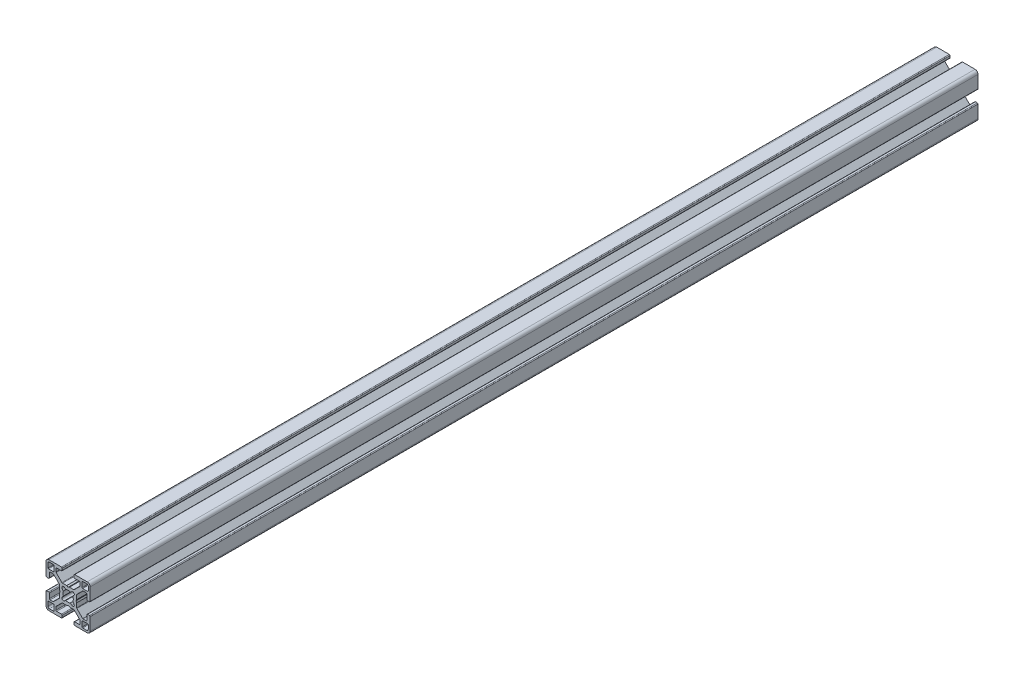
SolidWorks part; units mm, degrees
ref_plane "Plano frontal" through (0, 0, 0) normal (0, 0, 1) x (1, 0, 0)
ref_plane "Plano superior" through (0, 0, 0) normal (0, 1, 0) x (1, 0, 0)
ref_plane "Plano direito" through (0, 0, 0) normal (1, 0, 0) x (0, 0, -1)
ref_plane "Plano1"
sketch "Esboço1" plane through (0, 0, 0) normal (0, 0, 1) x (1, 0, 0)
  line L0 (-13, -15) -> (-4.508, -15)
  line L1 (-4, -14.492) -> (-4, -13.251)
  line L2 (-4.508, -12.743) -> (-7.742, -12.743)
  line L3 (-8.25, -12.235) -> (-8.25, -10.2642)
  line L4 (-8.1012, -9.905) -> (-4.1795, -5.9833)
  line L5 (-3.8203, -5.8345) -> (-0.949, -5.8345)
  line L6 (-0.949, -5.8345) -> (0, -5.325)
  line L7 (0, -5.325) -> (0.949, -5.8345)
  line L8 (0.949, -5.8345) -> (3.8216, -5.8345)
  line L9 (4.1808, -5.9833) -> (8.1012, -9.9037)
  line L10 (8.25, -10.2629) -> (8.25, -12.235)
  line L11 (7.742, -12.743) -> (4.508, -12.743)
  line L12 (4, -13.251) -> (4, -14.492)
  line L13 (4.508, -15) -> (13, -15)
  line L14 (15, -13) -> (15, -4.508)
  line L15 (14.492, -4) -> (13.251, -4)
  line L16 (12.743, -4.508) -> (12.743, -7.742)
  line L17 (12.235, -8.25) -> (10.2642, -8.25)
  line L18 (9.905, -8.1012) -> (5.9833, -4.1795)
  line L19 (5.8345, -3.8203) -> (5.8345, -0.949)
  line L20 (5.8345, -0.949) -> (5.325, 0)
  line L21 (5.325, 0) -> (5.8345, 0.949)
  line L22 (5.8345, 0.949) -> (5.8345, 3.8216)
  line L23 (5.9833, 4.1808) -> (9.9037, 8.1012)
  line L24 (10.2629, 8.25) -> (12.235, 8.25)
  line L25 (12.743, 7.742) -> (12.743, 4.508)
  line L26 (13.251, 4) -> (14.492, 4)
  line L27 (15, 4.508) -> (15, 13)
  line L28 (13, 15) -> (4.508, 15)
  line L29 (4, 14.492) -> (4, 13.251)
  line L30 (4.508, 12.743) -> (7.742, 12.743)
  line L31 (8.25, 12.235) -> (8.25, 10.2642)
  line L32 (8.1012, 9.905) -> (4.1795, 5.9833)
  line L33 (3.8203, 5.8345) -> (0.949, 5.8345)
  line L34 (0.949, 5.8345) -> (0, 5.325)
  line L35 (0, 5.325) -> (-0.949, 5.8345)
  line L36 (-0.949, 5.8345) -> (-3.8216, 5.8345)
  line L37 (-4.1808, 5.9833) -> (-8.1012, 9.9037)
  line L38 (-8.25, 10.2629) -> (-8.25, 12.235)
  line L39 (-7.742, 12.743) -> (-4.508, 12.743)
  line L40 (-4, 13.251) -> (-4, 14.492)
  line L41 (-4.508, 15) -> (-13, 15)
  line L42 (-15, 13) -> (-15, 4.508)
  line L43 (-14.492, 4) -> (-13.251, 4)
  line L44 (-12.743, 4.508) -> (-12.743, 7.742)
  line L45 (-12.235, 8.25) -> (-10.2642, 8.25)
  line L46 (-9.905, 8.1012) -> (-5.9833, 4.1795)
  line L47 (-5.8345, 3.8203) -> (-5.8345, 0.949)
  line L48 (-5.8345, 0.949) -> (-5.325, 0)
  line L49 (-5.325, 0) -> (-5.8345, -0.949)
  line L50 (-5.8345, -0.949) -> (-5.8345, -3.8216)
  line L51 (-5.9833, -4.1808) -> (-9.9037, -8.1012)
  line L52 (-10.2629, -8.25) -> (-12.235, -8.25)
  line L53 (-12.743, -7.742) -> (-12.743, -4.508)
  line L54 (-13.251, -4) -> (-14.492, -4)
  line L55 (-15, -4.508) -> (-15, -13)
  line L56 (9.5, 13.319) -> (9.5, 9.881)
  line L57 (9.881, 9.5) -> (13.319, 9.5)
  line L58 (13.7, 9.881) -> (13.7, 12.7)
  line L59 (12.7, 13.7) -> (9.881, 13.7)
  line L60 (9.5, -9.881) -> (9.5, -13.319)
  line L61 (9.881, -13.7) -> (12.7, -13.7)
  line L62 (13.7, -12.7) -> (13.7, -9.881)
  line L63 (13.319, -9.5) -> (9.881, -9.5)
  line L64 (-13.7, -9.881) -> (-13.7, -12.7)
  line L65 (-12.7, -13.7) -> (-9.881, -13.7)
  line L66 (-9.5, -13.319) -> (-9.5, -9.881)
  line L67 (-9.881, -9.5) -> (-13.319, -9.5)
  line L68 (-13.7, 12.7) -> (-13.7, 9.881)
  line L69 (-13.319, 9.5) -> (-9.881, 9.5)
  line L70 (-9.5, 9.881) -> (-9.5, 13.319)
  line L71 (-9.881, 13.7) -> (-12.7, 13.7)
  line L72 (-4.0107, 2.5139) -> (-3.1982, 1.4942)
  line L73 (-3.1982, -1.4942) -> (-4.0107, -2.5139)
  line L74 (-2.5139, -4.0107) -> (-1.4942, -3.1982)
  line L75 (1.4942, -3.1982) -> (2.5139, -4.0107)
  line L76 (4.0107, -2.5139) -> (3.1982, -1.4942)
  line L77 (3.1982, 1.4942) -> (4.0107, 2.5139)
  line L78 (2.5139, 4.0107) -> (1.4942, 3.1982)
  line L79 (-1.4942, 3.1982) -> (-2.5139, 4.0107)
  arc A0 (-15, -13) -> (-13, -15) centre (-13, -13) ccw
  arc A1 (-4.508, -15) -> (-4, -14.492) centre (-4.508, -14.492) ccw
  arc A2 (-4, -13.251) -> (-4.508, -12.743) centre (-4.508, -13.251) ccw
  arc A3 (-8.25, -12.235) -> (-7.742, -12.743) centre (-7.742, -12.235) ccw
  arc A4 (-8.1012, -9.905) -> (-8.25, -10.2642) centre (-7.742, -10.2642) ccw
  arc A5 (-3.8203, -5.8345) -> (-4.1795, -5.9833) centre (-3.8203, -6.3425) ccw
  arc A6 (4.1808, -5.9833) -> (3.8216, -5.8345) centre (3.8216, -6.3425) ccw
  arc A7 (8.25, -10.2629) -> (8.1012, -9.9037) centre (7.742, -10.2629) ccw
  arc A8 (7.742, -12.743) -> (8.25, -12.235) centre (7.742, -12.235) ccw
  arc A9 (4.508, -12.743) -> (4, -13.251) centre (4.508, -13.251) ccw
  arc A10 (4, -14.492) -> (4.508, -15) centre (4.508, -14.492) ccw
  arc A11 (13, -15) -> (15, -13) centre (13, -13) ccw
  arc A12 (15, -4.508) -> (14.492, -4) centre (14.492, -4.508) ccw
  arc A13 (13.251, -4) -> (12.743, -4.508) centre (13.251, -4.508) ccw
  arc A14 (12.235, -8.25) -> (12.743, -7.742) centre (12.235, -7.742) ccw
  arc A15 (9.905, -8.1012) -> (10.2642, -8.25) centre (10.2642, -7.742) ccw
  arc A16 (5.8345, -3.8203) -> (5.9833, -4.1795) centre (6.3425, -3.8203) ccw
  arc A17 (5.9833, 4.1808) -> (5.8345, 3.8216) centre (6.3425, 3.8216) ccw
  arc A18 (10.2629, 8.25) -> (9.9037, 8.1012) centre (10.2629, 7.742) ccw
  arc A19 (12.743, 7.742) -> (12.235, 8.25) centre (12.235, 7.742) ccw
  arc A20 (12.743, 4.508) -> (13.251, 4) centre (13.251, 4.508) ccw
  arc A21 (14.492, 4) -> (15, 4.508) centre (14.492, 4.508) ccw
  arc A22 (15, 13) -> (13, 15) centre (13, 13) ccw
  arc A23 (4.508, 15) -> (4, 14.492) centre (4.508, 14.492) ccw
  arc A24 (4, 13.251) -> (4.508, 12.743) centre (4.508, 13.251) ccw
  arc A25 (8.25, 12.235) -> (7.742, 12.743) centre (7.742, 12.235) ccw
  arc A26 (8.1012, 9.905) -> (8.25, 10.2642) centre (7.742, 10.2642) ccw
  arc A27 (3.8203, 5.8345) -> (4.1795, 5.9833) centre (3.8203, 6.3425) ccw
  arc A28 (-4.1808, 5.9833) -> (-3.8216, 5.8345) centre (-3.8216, 6.3425) ccw
  arc A29 (-8.25, 10.2629) -> (-8.1012, 9.9037) centre (-7.742, 10.2629) ccw
  arc A30 (-7.742, 12.743) -> (-8.25, 12.235) centre (-7.742, 12.235) ccw
  arc A31 (-4.508, 12.743) -> (-4, 13.251) centre (-4.508, 13.251) ccw
  arc A32 (-4, 14.492) -> (-4.508, 15) centre (-4.508, 14.492) ccw
  arc A33 (-13, 15) -> (-15, 13) centre (-13, 13) ccw
  arc A34 (-15, 4.508) -> (-14.492, 4) centre (-14.492, 4.508) ccw
  arc A35 (-13.251, 4) -> (-12.743, 4.508) centre (-13.251, 4.508) ccw
  arc A36 (-12.235, 8.25) -> (-12.743, 7.742) centre (-12.235, 7.742) ccw
  arc A37 (-9.905, 8.1012) -> (-10.2642, 8.25) centre (-10.2642, 7.742) ccw
  arc A38 (-5.8345, 3.8203) -> (-5.9833, 4.1795) centre (-6.3425, 3.8203) ccw
  arc A39 (-5.9833, -4.1808) -> (-5.8345, -3.8216) centre (-6.3425, -3.8216) ccw
  arc A40 (-10.2629, -8.25) -> (-9.9037, -8.1012) centre (-10.2629, -7.742) ccw
  arc A41 (-12.743, -7.742) -> (-12.235, -8.25) centre (-12.235, -7.742) ccw
  arc A42 (-12.743, -4.508) -> (-13.251, -4) centre (-13.251, -4.508) ccw
  arc A43 (-14.492, -4) -> (-15, -4.508) centre (-14.492, -4.508) ccw
  arc A44 (9.5, 9.881) -> (9.881, 9.5) centre (9.881, 9.881) ccw
  arc A45 (13.319, 9.5) -> (13.7, 9.881) centre (13.319, 9.881) ccw
  arc A46 (13.7, 12.7) -> (12.7, 13.7) centre (12.7, 12.7) ccw
  arc A47 (9.881, 13.7) -> (9.5, 13.319) centre (9.881, 13.319) ccw
  arc A48 (9.5, -13.319) -> (9.881, -13.7) centre (9.881, -13.319) ccw
  arc A49 (12.7, -13.7) -> (13.7, -12.7) centre (12.7, -12.7) ccw
  arc A50 (13.7, -9.881) -> (13.319, -9.5) centre (13.319, -9.881) ccw
  arc A51 (9.881, -9.5) -> (9.5, -9.881) centre (9.881, -9.881) ccw
  arc A52 (-13.7, -12.7) -> (-12.7, -13.7) centre (-12.7, -12.7) ccw
  arc A53 (-9.881, -13.7) -> (-9.5, -13.319) centre (-9.881, -13.319) ccw
  arc A54 (-9.5, -9.881) -> (-9.881, -9.5) centre (-9.881, -9.881) ccw
  arc A55 (-13.319, -9.5) -> (-13.7, -9.881) centre (-13.319, -9.881) ccw
  arc A56 (-13.7, 9.881) -> (-13.319, 9.5) centre (-13.319, 9.881) ccw
  arc A57 (-9.881, 9.5) -> (-9.5, 9.881) centre (-9.881, 9.881) ccw
  arc A58 (-9.5, 13.319) -> (-9.881, 13.7) centre (-9.881, 13.319) ccw
  arc A59 (-12.7, 13.7) -> (-13.7, 12.7) centre (-12.7, 12.7) ccw
  arc A60 (-2.5139, 4.0107) -> (-4.0107, 2.5139) centre (-3.142, 3.142) ccw
  arc A61 (-3.1982, 1.4942) -> (-3.1982, -1.4942) centre (0, 0) ccw
  arc A62 (-4.0107, -2.5139) -> (-2.5139, -4.0107) centre (-3.142, -3.142) ccw
  arc A63 (-1.4942, -3.1982) -> (1.4942, -3.1982) centre (0, 0) ccw
  arc A64 (2.5139, -4.0107) -> (4.0107, -2.5139) centre (3.142, -3.142) ccw
  arc A65 (3.1982, -1.4942) -> (3.1982, 1.4942) centre (0, 0) ccw
  arc A66 (4.0107, 2.5139) -> (2.5139, 4.0107) centre (3.142, 3.142) ccw
  arc A67 (1.4942, 3.1982) -> (-1.4942, 3.1982) centre (0, 0) ccw
extrude "Extrusion1" add sketch "Esboço1" against normal blind 603 contours L54 A43 L55 A0 L0 A1 L1 A2 L2 A3 L3 A4 L4 A5 L5 L6 L7 L8 A6 L9 A7 L10 A8 L11 A9 L12 A10 L13 A11 L14 A12 L15 A13 L16 A14 L17 A15 L18 A16 L19 L20 L21 L22 A17 L23 A18 L24 A19 L25 A20 L26 region at (-14.1142, -14.1142, 0)
